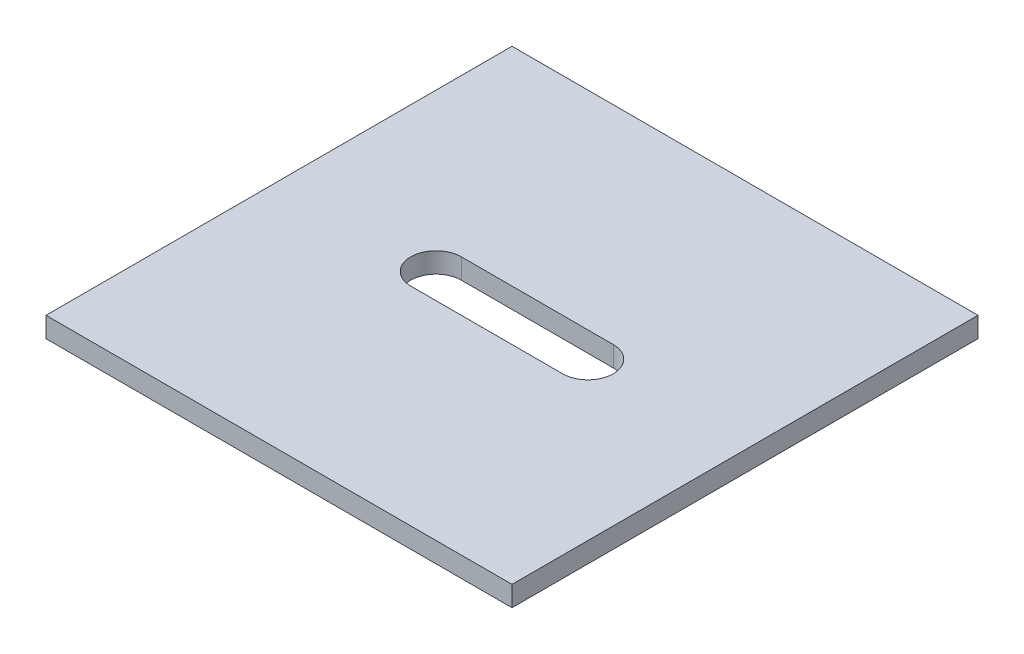
SolidWorks part; units mm, degrees
material "Pine"
ref_plane "Front Plane" through (0, 0, 0) normal (0, 0, 1) x (1, 0, 0)
ref_plane "Top Plane" through (0, 0, 0) normal (0, 1, 0) x (1, 0, 0)
ref_plane "Right Plane" through (0, 0, 0) normal (1, 0, 0) x (0, 0, -1)
sketch "Sketch2" plane through (0, 0, 0) normal (0, 1, 0) x (1, 0, 0)
  line L4 (93, 138) -> (183, 138) construction
  line L5 (0, 0) -> (276, 0)
  line L6 (0, 0) -> (0, 276)
  line L7 (0, 276) -> (276, 276)
  line L8 (276, 0) -> (276, 276)
  line L9 (93, 153) -> (183, 153)
  line L10 (93, 123) -> (183, 123)
  arc A0 (93, 153) -> (93, 123) centre (93, 138) ccw
  arc A1 (183, 123) -> (183, 153) centre (183, 138) ccw
  point P7 (138, 138)
  point P12 (0, 0)
  dimension "D3" = 138
  dimension "D5" = 15
  dimension "D1" = 276
  dimension "D2" = 276
  dimension "D4" = 93
  dimension "D6" = 90
extrude "Boss-Extrude1" add sketch "Sketch2" along normal blind 12 contours L7 L8 L5 L6
extrude "Cut-Extrude1" cut sketch "Sketch2<3>" along normal up to surface (12 mm away) contours A0 L10 A1 L9 up to face at (138, 12, -138)
sketch "Sketch2<3>" plane through (0, 0, 0) normal (0, 1, 0) x (1, 0, 0) same geometry as "Sketch2"
